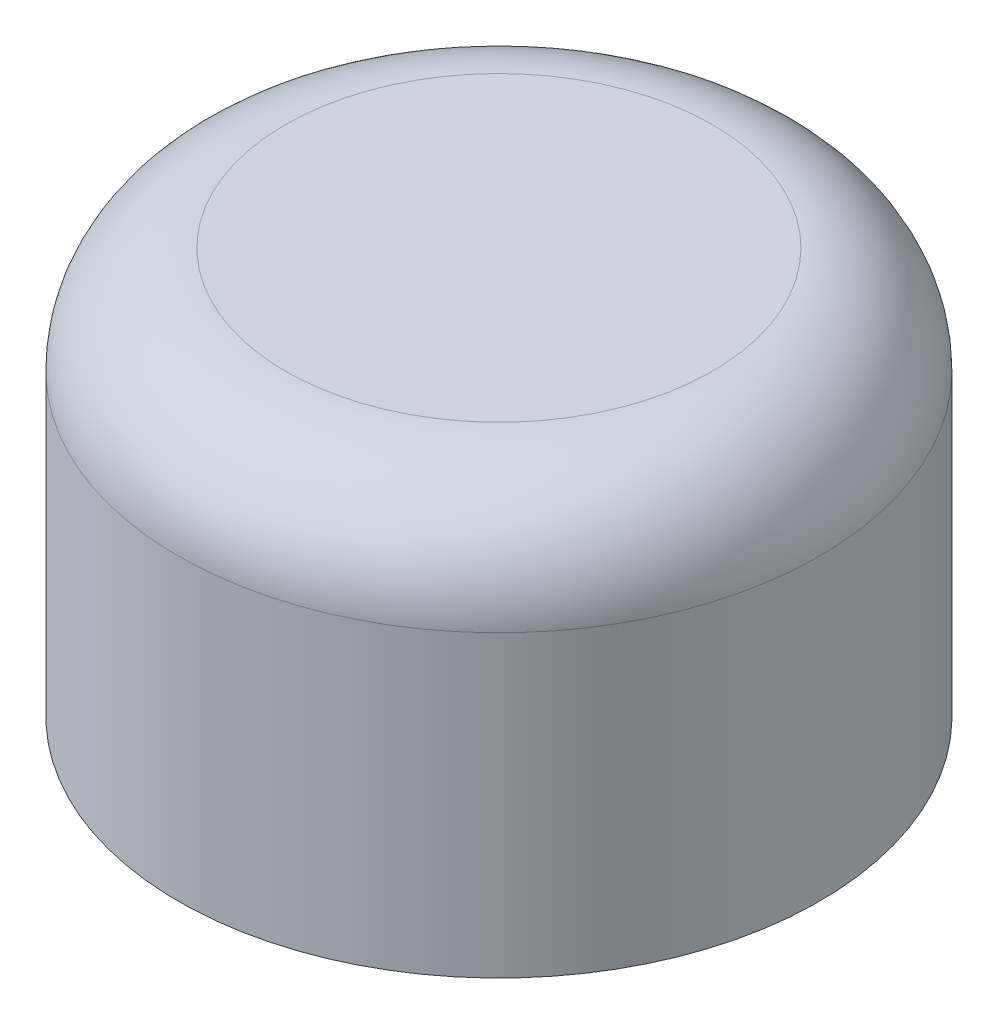
SolidWorks part; units mm, degrees
material "ABS"
ref_plane "正面" through (0, 0, 0) normal (0, 0, 1) x (1, 0, 0)
ref_plane "平面" through (0, 0, 0) normal (0, 1, 0) x (1, 0, 0)
ref_plane "右側面" through (0, 0, 0) normal (1, 0, 0) x (0, 0, -1)
sketch "ｽｹｯﾁ1" plane through (0, 0, 0) normal (0, 0, 1) x (1, 0, 0)
  line L1 (0, 20) -> (10, 20)
  line L3 (15, 15) -> (15, 1)
  line L4 (15, 1) -> (14, 1)
  line L5 (14, 1) -> (14, 3.5)
  line L7 (0, 20) -> (0, 19)
  line L8 (0, 19) -> (10, 19)
  line L9 (14, 3.5) -> (0, 3.5)
  line L10 (0, 3.5) -> (0, 6.5)
  line L11 (0, 6.5) -> (14, 6.5)
  line L12 (14, 6.5) -> (14, 15)
  line L13 (8, 0) -> (8, 4.2574) construction
  arc A0 (10, 20) -> (15, 15) centre (10, 15) cw
  arc A2 (10, 19) -> (14, 15) centre (10, 15) cw
  dimension "D4" = 20
  dimension "D7" = 8
  dimension "D1" = 19
  dimension "D2" = 10
  dimension "D3" = 1
  dimension "D5" = 15
  dimension "D6" = 1
  dimension "D8" = 3.5
  dimension "D9" = 3
revolve "回転1" add sketch "ｽｹｯﾁ1" angle 360 about L10
sketch "ｽｹｯﾁ2" plane through (0, 6.5, 0) normal (0, 1, 0) x (1, 0, 0)
  line L0 (-0.75, 0.75) -> (-0.75, 8)
  line L1 (0.75, -8) -> (-0.75, -8)
  line L2 (0.75, -8) -> (0.75, -0.75)
  line L3 (0.75, 8) -> (-0.75, 8)
  line L4 (-0.75, -8) -> (-0.75, -0.75)
  line L5 (0.75, -8) -> (-0.75, 8) construction
  line L6 (0.75, 8) -> (-0.75, -8) construction
  line L7 (-8, 0.75) -> (-0.75, 0.75)
  line L8 (-8, 0.75) -> (-8, -0.75)
  line L9 (-8, -0.75) -> (-0.75, -0.75)
  line L10 (8, 0.75) -> (8, -0.75)
  line L11 (-8, 0.75) -> (8, -0.75) construction
  line L12 (-8, -0.75) -> (8, 0.75) construction
  line L13 (0.75, 0.75) -> (8, 0.75)
  line L14 (0.75, 0.75) -> (0.75, 8)
  line L15 (0.75, -0.75) -> (8, -0.75)
  point P0 (0, 0)
  point P5 (0, 0)
  dimension "D1" = 16
  dimension "D2" = 16
  dimension "D3" = 1.5
  dimension "D4" = 1.5
extrude "ﾎﾞｽ - 押し出し1" add sketch "ｽｹｯﾁ2" along normal blind 13
